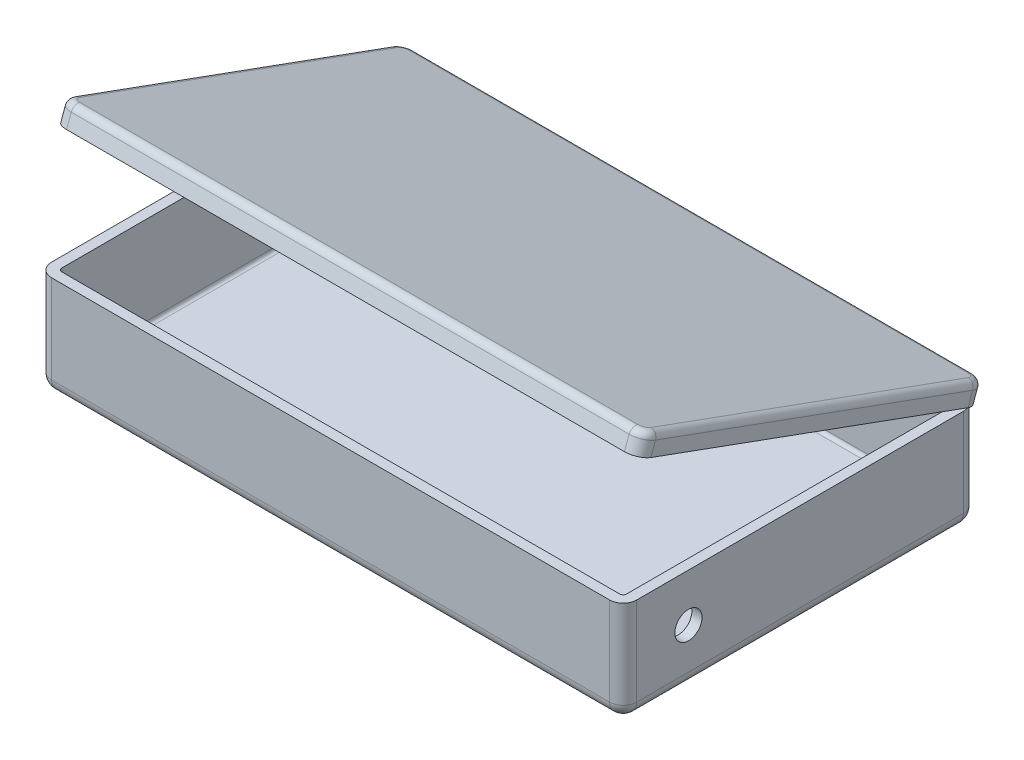
SolidWorks part; units mm, degrees
material "Acrylic (Medium-high impact)"
ref_plane "Front" through (0, 0, 0) normal (0, 0, 1) x (1, 0, 0)
ref_plane "Top" through (0, 0, 0) normal (0, 1, 0) x (1, 0, 0)
ref_plane "Right" through (0, 0, 0) normal (1, 0, 0) x (0, 0, -1)
sketch "Sketch1" plane through (0, 0, 0) normal (0, 1, 0) x (1, 0, 0)
  line L1 (-136.525, 82.55) -> (136.525, 82.55)
  line L2 (-136.525, 82.55) -> (-136.525, -82.55)
  line L3 (-136.525, -82.55) -> (136.525, -82.55)
  line L4 (136.525, 82.55) -> (136.525, -82.55)
  line L5 (-136.525, 82.55) -> (136.525, -82.55) construction
  line L6 (-136.525, -82.55) -> (136.525, 82.55) construction
  point P0 (0, 0)
  dimension "D1" = 273.05
  dimension "D2" = 165.1
extrude "Boss-Extrude1" add sketch "Sketch1" along normal blind 47.625
fillet "Fillet1" radius 6.35 8 edges at (0, 0, -82.55) (-136.525, 0, 0) (0, 0, 82.55) (136.525, 0, 0) (-136.525, 23.8125, -82.55) (136.525, 23.8125, -82.55) (136.525, 23.8125, 82.55) (-136.525, 23.8125, 82.55)
shell "Shell1" thickness 4.7625 removed face at (0, 47.625, 0)
sketch "Sketch2" plane through (0, 0, 0) normal (1, 0, 0) x (0, 0, -1)
  line L0 (82.55, 47.625) -> (84.3461, 45.8289) construction
  line L2 (84.3461, 45.8289) -> (-75.5708, 104.0339)
  line L3 (-75.5708, 104.0339) -> (-72.3131, 112.9845)
  line L4 (-72.3131, 112.9845) -> (87.6038, 54.7795)
  line L5 (84.3461, 45.8289) -> (87.6038, 54.7795)
  line L6 (82.55, 47.625) -> (82.55, 45.8289) construction
  line L7 (82.55, 45.8289) -> (84.3461, 45.8289) construction
  line L8 (-76.2, 47.625) -> (76.2, 47.625) construction
  dimension "D1" = 2.54
  dimension "D2" = 9.525
  dimension "D3" = 170.18
  dimension "D4" = 20
extrude "LID OPENING ANGLE CONTROL" add sketch "Sketch2" along normal mid plane 273.05 separate body
fillet "Fillet2" radius 6.35 4 edges at (136.525, 50.3042, -85.9749) (-136.525, 50.3042, -85.9749) (136.525, 108.5092, 73.942) (-136.525, 108.5092, 73.942)
fillet "Fillet3" radius 3.175 8 edges at (134.6651, 112.3484, 70.5654) (0, 112.9845, 72.3131) (-134.6651, 112.3484, 70.5654) (-136.525, 83.882, -7.6453) (-134.6651, 55.4156, -85.8561) (0, 54.7795, -87.6038) (134.6651, 55.4156, -85.8561) (136.525, 83.882, -7.6453)
shell "Shell2" thickness 2.54 removed face at (0, 74.9314, -4.3876)
sketch "Sketch3" plane through (136.525, 0, 0) normal (1, 0, 0) x (0, 0, -1)
  line L0 (76.2, 0) -> (-76.2, 0) construction
  line L1 (-82.55, 6.35) -> (-82.55, 47.625) construction
  circle A0 centre (-52.07, 25.4) radius 6.35
  dimension "D1" = 12.7
  dimension "D2" = 25.4
  dimension "D3" = 30.48
extrude "Cut-Extrude1" cut sketch "Sketch3" against normal up to next (4.7625 mm away)
